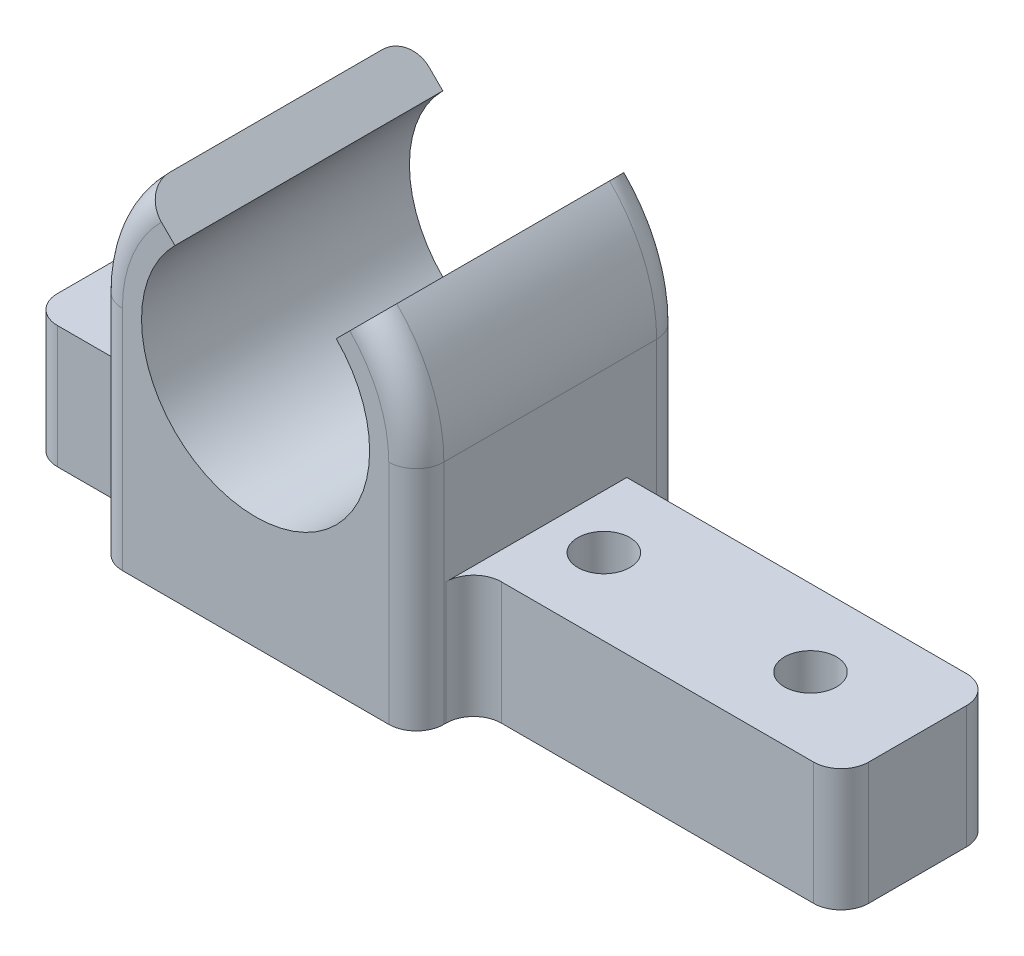
SolidWorks part; units mm, degrees
material "ABS"
ref_plane "Front Plane" through (0, 0, 0) normal (0, 0, 1) x (1, 0, 0)
ref_plane "Top Plane" through (0, 0, 0) normal (0, 1, 0) x (1, 0, 0)
ref_plane "Right Plane" through (0, 0, 0) normal (1, 0, 0) x (0, 0, -1)
sketch "Sketch1" plane through (0, 0, 0) normal (0, 1, 0) x (1, 0, 0)
  line L0 (73.3937, 5) -> (73.3937, -5)
  line L1 (66.3937, 3.2) -> (63.6225, 1.6) construction
  line L2 (63.6225, 1.6) -> (63.6225, -1.6) construction
  line L3 (63.6225, -1.6) -> (66.3937, -3.2) construction
  line L4 (66.3937, -3.2) -> (69.165, -1.6) construction
  line L5 (69.165, -1.6) -> (69.165, 1.6) construction
  line L6 (69.165, 1.6) -> (66.3937, 3.2) construction
  line L7 (73.3937, -5) -> (20.3937, -5)
  line L9 (73.3937, 5) -> (20.3937, 5)
  line L10 (20.3937, -5) -> (20.3937, 5)
  line L12 (73.3937, 3.1538) -> (20.3937, -5) construction
  circle A0 centre (52.8937, 0) radius 1.7
  circle A1 centre (24.8937, 0) radius 1.7
  circle A2 centre (66.3937, 0) radius 1.7
  circle A3 centre (66.3937, 0) radius 3.2 construction
  dimension "D1" = 3.4
  dimension "D2" = 3.4
  dimension "D3" = 28
  dimension "D4" = 3.4
  dimension "D5" = 13.5
  dimension "D7" = 4.5
  dimension "D8" = 7
  dimension "D9" = 5
  dimension "D6" = 10
extrude "Boss-Extrude1" add sketch "Sketch1" along normal blind 8
sketch "Sketch2" plane through (0, 0, -5) normal (0, 0, -1) x (-1, 0, 0)
  line L1 (-33.6258, 14.7679) -> (-31.4691, 16.9246)
  line L2 (-20.3937, 8) -> (-73.3937, 8) construction
  line L3 (-23.1937, 8) -> (-26.5937, 8) construction
  line L4 (-23.1937, 8) -> (-26.5937, 8)
  line L5 (-24.8937, 8) -> (-24.8937, 21.3762)
  line L6 (-44.1617, 14.7679) -> (-46.3184, 16.9246)
  line L12 (-49.3937, 0) -> (-28.3937, 0)
  line L13 (-28.3937, 9.5) -> (-28.3937, 0)
  line L15 (-49.3937, 9.5) -> (-49.3937, 0)
  arc A0 (-44.1617, 14.7679) -> (-33.6258, 14.7679) centre (-38.8937, 9.5) ccw
  arc A1 (-46.3184, 16.9246) -> (-49.3937, 9.5) centre (-38.8937, 9.5) ccw
  arc A2 (-28.3937, 9.5) -> (-31.4691, 16.9246) centre (-38.8937, 9.5) ccw
  dimension "D1" = 14.9
  dimension "D2" = 14
  dimension "D3" = 45
  dimension "D4" = 21
extrude "Boss-Extrude2" add sketch "Sketch2" along normal blind 3.75 and the other way offset from surface (13.75 mm away) 3.75 contours A2 L1 A0 L6 A1 L15 L12 L13 other way up to face at (46.8937, 4, 5)
sketch "Sketch3" plane through (0, 0, 5) normal (0, 0, 1) x (1, 0, 0)
  line L1 (46.1912, 8) -> (31.5963, 8)
  line L2 (46.1912, 8) -> (31.5963, 8)
  arc A1 (31.5963, 8) -> (46.1912, 8) centre (38.8937, 9.5) ccw
  arc A2 (31.5963, 8) -> (46.1912, 8) centre (38.8937, 9.5) ccw
  dimension "D1" = 0
extrude "Cut-Extrude1" cut sketch "Sketch3" against normal through all
sketch "Sketch4" plane through (0, 0, 0) normal (0, -1, 0) x (1, 0, 0)
  line L1 (63.6225, 1.6) -> (63.6225, -1.6)
  line L2 (63.6225, -1.6) -> (66.3937, -3.2)
  line L3 (66.3937, -3.2) -> (69.165, -1.6)
  line L4 (69.165, -1.6) -> (69.165, 1.6)
  line L5 (69.165, 1.6) -> (66.3937, 3.2)
  line L6 (66.3937, 3.2) -> (63.6225, 1.6)
  circle A0 centre (66.3937, 0) radius 3.2 construction
  dimension "D1" = 6.4
extrude "Cut-Extrude2" cut sketch "Sketch4" along normal blind 7.844 from surface at -8 starting at face at (61.3937, 8, 0)
sketch "Sketch5" plane through (0, 0, 0) normal (0, -1, 0) x (1, 0, 0)
  line L12 (73.3937, 5) -> (49.3937, 5)
  line L13 (49.3937, 5) -> (49.3937, 8.75)
  line L14 (49.3937, 8.75) -> (28.3937, 8.75)
  line L15 (28.3937, 8.75) -> (28.3937, 5)
  line L16 (28.3937, 5) -> (20.3937, 5)
  line L17 (20.3937, 5) -> (20.3937, -5)
  line L18 (20.3937, -5) -> (28.3937, -5)
  line L19 (28.3937, -5) -> (28.3937, -8.75)
  line L20 (28.3937, -8.75) -> (49.3937, -8.75)
  line L21 (49.3937, -8.75) -> (49.3937, -5)
  line L22 (49.3937, -5) -> (73.3937, -5)
  line L23 (73.3937, -5) -> (73.3937, 5)
  line L24 (73.3937, 5) -> (49.3937, 5)
  line L25 (49.3937, 5) -> (49.3937, 8.75)
  line L26 (49.3937, 8.75) -> (28.3937, 8.75)
  line L27 (28.3937, 8.75) -> (28.3937, 5)
  line L28 (28.3937, 5) -> (20.3937, 5)
  line L29 (20.3937, 5) -> (20.3937, -5)
  line L30 (20.3937, -5) -> (28.3937, -5)
  line L31 (28.3937, -5) -> (28.3937, -8.75)
  line L32 (28.3937, -8.75) -> (49.3937, -8.75)
  line L33 (49.3937, -8.75) -> (49.3937, -5)
  line L34 (49.3937, -5) -> (73.3937, -5)
  line L35 (73.3937, -5) -> (73.3937, 5)
  circle A0 centre (66.3937, 0) radius 1.7 construction
  circle A1 centre (52.8937, 0) radius 1.7 construction
  circle A2 centre (24.8937, 0) radius 1.7 construction
  circle A3 centre (66.3937, 0) radius 1.7
  circle A4 centre (52.8937, 0) radius 1.7
  circle A5 centre (24.8937, 0) radius 1.7
  dimension "D1" = 0
extrude "Boss-Extrude3" add sketch "Sketch5" along normal blind 5.34
sketch "Sketch6" plane through (0, 8, 0) normal (0, 1, 0) x (1, 0, 0)
  circle A0 centre (66.3937, 0) radius 3.2
extrude "Cut-Extrude3" cut sketch "Sketch6" against normal offset from surface (4.844 mm away) 3 up to face at (66.3937, 0.156, 1.7)
chamfer "Chamfer3" distance 0.4 angle 45 6 edges at (69.5937, 3.156, 0) (67.9937, 3.156, 2.7713) (64.7937, 3.156, 2.7713) (63.1937, 3.156, 0) (64.7937, 3.156, -2.7713) (67.9937, 3.156, -2.7713)
fillet "Fillet2" radius 1.8 15 edges at (48.5945, 13.5182, 8.75) (29.193, 13.5182, 8.75) (29.193, 13.5182, -8.75) (48.5945, 13.5182, -8.75) (49.3937, 1.33, 5) (49.3937, 2.08, 8.75) (28.3937, 2.08, 8.75) (28.3937, 1.33, 5) (28.3937, 1.33, -5) (28.3937, 2.08, -8.75) (49.3937, 2.08, -8.75) (73.3937, 1.33, -5) (73.3937, 1.33, 5) (20.3937, 1.33, -5) (20.3937, 1.33, 5)
sketch "Sketch8" plane through (0, 8, 0) normal (0, 1, 0) x (1, 0, 0)
  line L4 (26.5937, 5) -> (22.1937, 5)
  line L5 (20.3937, 3.2) -> (20.3937, -3.2)
  line L6 (22.1937, -5) -> (26.5937, -5)
  line L7 (28.3937, -6.8) -> (28.3937, 6.8)
  line L8 (26.5937, 5) -> (22.1937, 5)
  line L9 (20.3937, 3.2) -> (20.3937, -3.2)
  line L10 (22.1937, -5) -> (26.5937, -5)
  line L11 (28.3937, -6.8) -> (28.3937, 6.8)
  line L12 (73.3937, -3.2) -> (73.3937, 3.2)
  line L13 (71.5937, 5) -> (49.3937, 5)
  line L14 (49.3937, 5) -> (49.3937, -6.8)
  line L15 (51.1937, -5) -> (71.5937, -5)
  line L16 (73.3937, -3.2) -> (73.3937, 3.2)
  line L17 (71.5937, 5) -> (49.3937, 5)
  line L18 (49.3937, 5) -> (49.3937, -6.8)
  line L19 (51.1937, -5) -> (71.5937, -5)
  circle A0 centre (24.8937, 0) radius 1.7 construction
  circle A1 centre (24.8937, 0) radius 1.7
  arc A4 (22.1937, 5) -> (20.3937, 3.2) centre (22.1937, 3.2) ccw
  arc A5 (20.3937, -3.2) -> (22.1937, -5) centre (22.1937, -3.2) ccw
  arc A6 (28.3937, -6.8) -> (26.5937, -5) centre (26.5937, -6.8) ccw
  arc A7 (26.5937, 5) -> (28.3937, 6.8) centre (26.5937, 6.8) ccw
  arc A8 (22.1937, 5) -> (20.3937, 3.2) centre (22.1937, 3.2) ccw
  arc A9 (20.3937, -3.2) -> (22.1937, -5) centre (22.1937, -3.2) ccw
  arc A10 (28.3937, -6.8) -> (26.5937, -5) centre (26.5937, -6.8) ccw
  arc A11 (26.5937, 5) -> (28.3937, 6.8) centre (26.5937, 6.8) ccw
  arc A15 (73.3937, 3.2) -> (71.5937, 5) centre (71.5937, 3.2) ccw
  arc A16 (51.1937, -5) -> (49.3937, -6.8) centre (51.1937, -6.8) ccw
  arc A17 (71.5937, -5) -> (73.3937, -3.2) centre (71.5937, -3.2) ccw
  arc A18 (73.3937, 3.2) -> (71.5937, 5) centre (71.5937, 3.2) ccw
  arc A19 (51.1937, -5) -> (49.3937, -6.8) centre (51.1937, -6.8) ccw
  arc A20 (71.5937, -5) -> (73.3937, -3.2) centre (71.5937, -3.2) ccw
  dimension "D1" = 0
  dimension "D3" = 0
extrude "Cut-Extrude5" cut sketch "Sketch8" against normal offset from surface (5.344 mm away) 2.5 up to face at (66.3937, 0.156, 1.7)
sketch "Sketch10" plane through (0, 0.156, 0) normal (0, 1, 0) x (1, 0, 0)
  line L6 (69.165, -1.6) -> (69.165, 1.6)
  line L7 (69.165, 1.6) -> (66.3937, 3.2)
  line L8 (66.3937, 3.2) -> (63.6225, 1.6)
  line L9 (63.6225, 1.6) -> (63.6225, -1.6)
  line L10 (63.6225, -1.6) -> (66.3937, -3.2)
  line L11 (66.3937, -3.2) -> (69.165, -1.6)
  line L12 (69.165, -1.6) -> (69.165, 1.6)
  line L13 (69.165, 1.6) -> (66.3937, 3.2)
  line L14 (66.3937, 3.2) -> (63.6225, 1.6)
  line L15 (63.6225, 1.6) -> (63.6225, -1.6)
  line L16 (63.6225, -1.6) -> (66.3937, -3.2)
  line L17 (66.3937, -3.2) -> (69.165, -1.6)
  circle A0 centre (66.3937, 0) radius 1.7 construction
  circle A1 centre (66.3937, 0) radius 1.7
  dimension "D1" = 0
extrude "Boss-Extrude4" add sketch "Sketch10" along normal up to surface (2.5 mm away) up to face at (62.9041, 2.656, 0.9182)
sketch "Sketch11" plane through (0, -5.34, 0) normal (0, -1, 0) x (-1, 0, 0)
  line L1 (-68.9918, -1.5) -> (-66.3937, -3)
  line L2 (-66.3937, -3) -> (-63.7957, -1.5)
  line L3 (-63.7957, -1.5) -> (-63.7957, 1.5)
  line L4 (-63.7957, 1.5) -> (-66.3937, 3)
  line L5 (-66.3937, 3) -> (-68.9918, 1.5)
  line L6 (-68.9918, 1.5) -> (-68.9918, -1.5)
  circle A0 centre (-66.3937, 0) radius 3 construction
  dimension "D1" = 6
extrude "Cut-Extrude6" cut sketch "Sketch11" against normal blind 4
chamfer "Chamfer4" distance 1.1 angle 45 1 edges at (66.3937, -1.34, -1.7)
chamfer "Chamfer5" distance 0.5 angle 45 8 edges at (68.9918, -5.34, 0) (67.6928, -5.34, 2.25) (65.0947, -5.34, 2.25) (63.7957, -5.34, 0) (65.0947, -5.34, -2.25) (67.6928, -5.34, -2.25) (24.8937, -5.34, -1.7) (52.8937, -5.34, -1.7)
